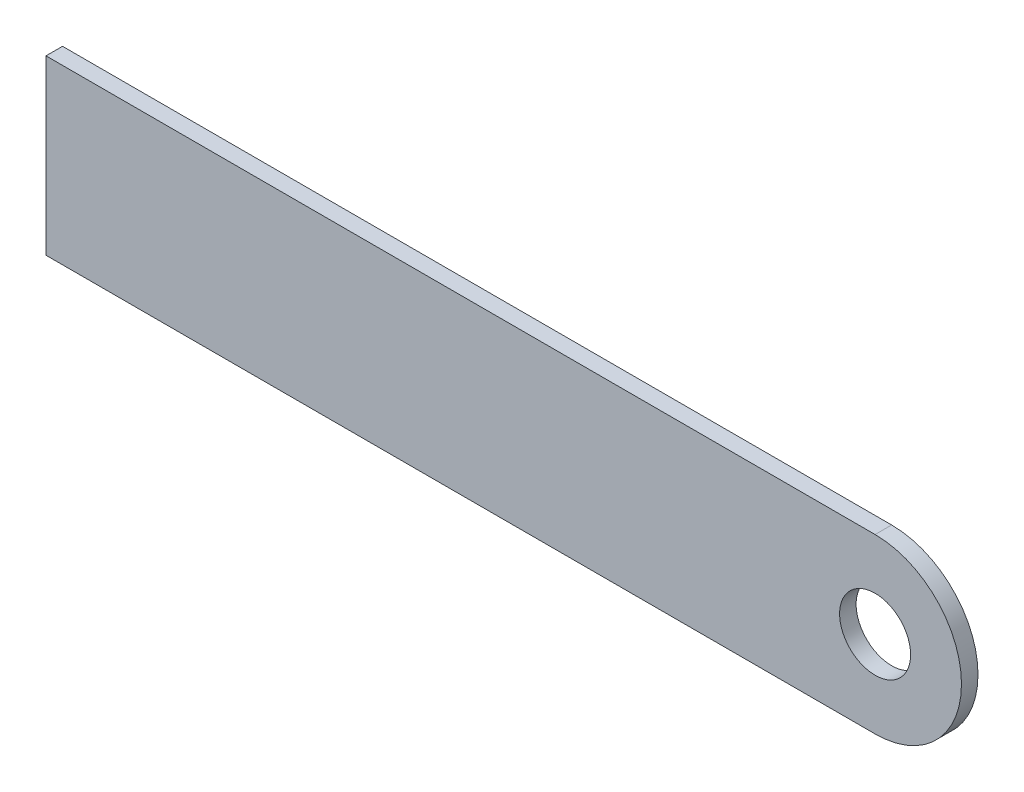
SolidWorks part; units mm, degrees
ref_plane "Front Plane" through (0, 0, 0) normal (0, 0, 1) x (1, 0, 0)
ref_plane "Top Plane" through (0, 0, 0) normal (0, 1, 0) x (1, 0, 0)
ref_plane "Right Plane" through (0, 0, 0) normal (1, 0, 0) x (0, 0, -1)
sketch "Sketch1" plane through (0, 0, 0) normal (0, 0, 1) x (1, 0, 0)
  line L0 (76.2, 11.2014) -> (76.2, 15.875) construction
  line L1 (0, 0) -> (76.2, 0)
  line L2 (0, 0) -> (0, 15.875)
  line L3 (0, 15.875) -> (76.2, 15.875)
  line L4 (76.2, 0) -> (76.2, 4.6736) construction
  line L5 (76.2, 4.6736) -> (76.2, 11.2014) construction
  arc A0 (76.2, 15.875) -> (76.2, 0) centre (76.2, 7.9375) cw
  circle A1 centre (76.2, 7.9375) radius 3.2639
  dimension "D2" = 6.5278
  dimension "D1" = 15.875
  dimension "D3" = 76.2
base flange "Base-Flange1" sketch "Sketch1" thickness 1.5189 reverse thickness direction no parameters "D1"=1.905
sketch "Bend-Lines1" [suppressed] plane through (0, 0, 0) normal (0, 1, 0) x (1, 0, 0)
sketch "Bounding-Box1" [suppressed] plane through (0, 0, 0) normal (0, 1, 0) x (1, 0, 0)
sheet metal parameters "Sheet-Metal1" thickness 1.5189 parameters "D1"=1.905
flat pattern "Flat-Pattern1" [suppressed]
sketch "Bend-Lines2" plane through (0, 0, 0) normal (0, 1, 0) x (1, 0, 0)
sketch3d "Bounding-Box2" [suppressed]
  line L0 (76.2, -7.9375, 0) -> (-7.9374, -7.9375, 0) construction
  line L1 (76.2, 7.9375, 0) -> (-7.9374, 7.9375, 0) construction
  line L2 (76.2, -7.9375, 0) -> (76.2, 7.9375, 0) construction
  line L3 (-7.9374, -7.9375, 0) -> (-7.9374, 7.9375, 0) construction
